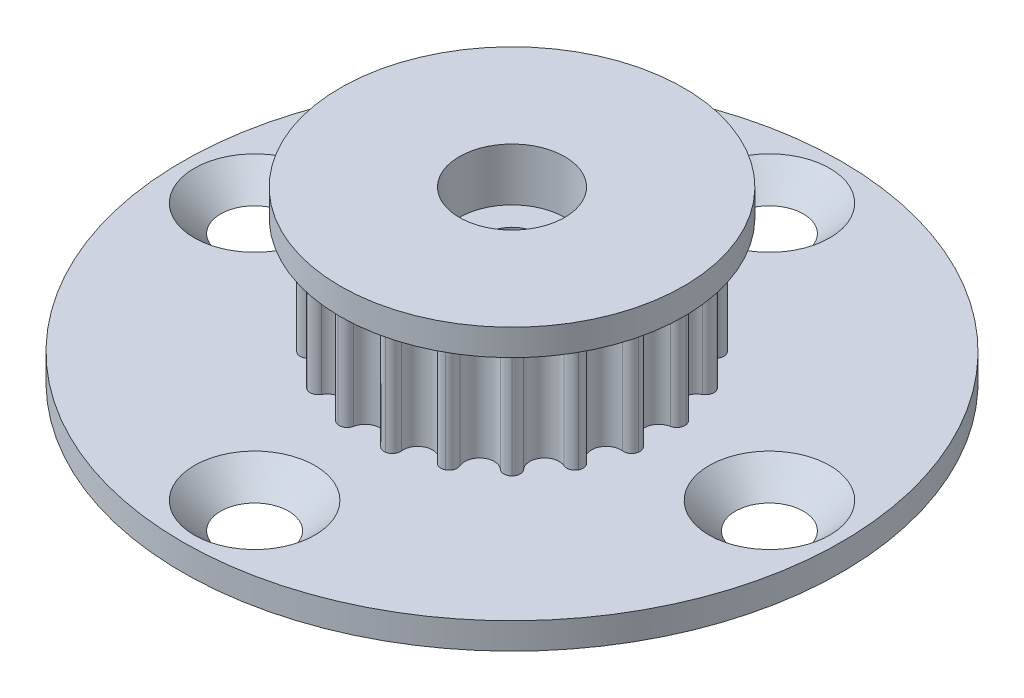
SolidWorks part; units mm, degrees
ref_plane "Front Plane" through (0, 0, 0) normal (0, 0, 1) x (1, 0, 0)
ref_plane "Top Plane" through (0, 0, 0) normal (0, 1, 0) x (1, 0, 0)
ref_plane "Right Plane" through (0, 0, 0) normal (1, 0, 0) x (0, 0, -1)
sketch "Sketch1" plane through (0, 0, 0) normal (0, 1, 0) x (1, 0, 0)
  line L0 (0, 0) -> (0, 9.1676) construction
  line L1 (0, 0) -> (2.731, 8.405) construction
  circle A0 centre (0, 0) radius 9.1676 construction
  circle A1 centre (0, 0) radius 7.9476 construction
  circle A2 centre (0, 8.8376) radius 0.89 construction
  circle A5 centre (2.731, 8.405) radius 0.89 construction
  arc A6 (0, 7.9476) -> (0.8721, 8.6598) centre (0, 8.8376) ccw
  arc A7 (0.8721, 8.6598) -> (1.4405, 9.0537) centre (1.362, 8.5599) cw
  arc A8 (1.4277, 9.0557) -> (1.8466, 8.5054) centre (1.3498, 8.5618) cw
  arc A9 (2.4559, 7.5586) -> (1.8466, 8.5054) centre (2.731, 8.405) cw
  arc A10 (1.4405, 9.0537) -> (1.4277, 9.0557) centre (0, 0) cw
  arc A11 (0, 7.9476) -> (2.4559, 7.5586) centre (0, 0) ccw
  dimension "D1" = 18.3352
  dimension "D3" = 1.78
  dimension "D4" = 0.5
  dimension "D2" = 1.22
  dimension "D5" = 18
extrude "Boss-Extrude1" add sketch "Sketch1" along normal mid plane 7.112 contours A6 A11 A9 A8 A7 region at (0.0089, 0, -0.0564)
ref_axis "Axis1" through (0, 3.3, 0) along (0, -1, 0)
pattern_circular "CirPattern1" count 20 over 360 about axis through (0, 3.3, 0) along (0, -1, 0) of "Boss-Extrude1"
sketch "Sketch2" plane through (0, 0, 0) normal (1, 0, 0) x (0, 0, -1)
  line L10 (0, 3.5) -> (10.3423, 3.5) construction
  line L11 (0, 3.5) -> (0, 5.0875) construction
  line L12 (0, 5.0875) -> (10.3423, 5.0875) construction
  line L15 (10.3423, 3.5) -> (10.3423, 5.0875) construction
  line L20 (0, 3.3) -> (0, -3.3) construction
  line L22 (10.3423, 5.0875) -> (0, 5.0875)
  line L23 (10.3423, 5.0875) -> (10.3423, 3.5)
  line L24 (10.3423, 3.5) -> (0, 3.5)
  line L25 (0, 5.0875) -> (0, 3.5)
  dimension "D1" = 1.5875
  dimension "D2" = 10.3423
  dimension "D3" = 3.5
revolve "Revolve3" add sketch "Sketch2" angle 360 about axis through (0, 3.3, 0) along (0, -1, 0) region at (0, 4.2937, -5.1712)
mirror "Mirror1" about plane through (0, 0, 0) normal (0, 1, 0) of "Revolve3"
sketch "Sketch9" plane through (0, -5.0875, 0) normal (0, -1, 0) x (1, 0, 0)
  circle A0 centre (0, 0) radius 19.8438
  circle A1 centre (0, 0) radius 1.5
  dimension "D1" = 3
  dimension "D2" = 39.6875
extrude "Boss-Extrude2" add sketch "Sketch9" against normal up to surface (1.5875 mm away) up to face at (0, -3.5, 0)
sketch "Sketch3" plane through (0, 0, 0) normal (0, 1, 0) x (1, 0, 0)
  circle A0 centre (-15.5, 0) radius 1.7462
  circle A3 centre (0, 15.5) radius 1.7462
  circle A4 centre (15.5, 0) radius 1.7463
  circle A5 centre (0, -15.5) radius 1.7462
  dimension "D3" = 3.4925
  dimension "D1" = 15.5
  dimension "D4" = 4
extrude "Cut-Extrude1" cut sketch "Sketch3" against normal through all both and the other way through all
ref_axis "Axis2" through (-15.5, -5.0875, 0) along (0, 1, 0)
sketch "Sketch6" plane through (0, 0, 0) normal (0, 0, 1) x (1, 0, 0)
  line L0 (-19.1322, -3.5) -> (-11.8678, -3.5) construction
  line L1 (-13.7538, -3.5) -> (-17.2462, -3.5) construction
  line L2 (-11.8678, -3.5) -> (-15.5, -7.1322)
  line L3 (-15.5, -7.1322) -> (-19.1322, -3.5) construction
  line L4 (-18.548, -4.0842) -> (-12.452, -4.0842) construction
  line L5 (-17.2462, -3.998) -> (-13.7538, -3.998) construction
  line L8 (-15.5, -7.1322) -> (-15.5, -3.5)
  line L9 (-15.5, -3.5) -> (-11.8678, -3.5)
  line L10 (-15.5, -5.0875) -> (-15.5, -3.5) construction
  line L12 (-17.2462, -3.5) -> (-17.2462, -5.0875) construction
  line L13 (-13.7538, -5.0875) -> (-13.7538, -3.5) construction
  point P2 (-15.5, -3.998)
  dimension "D1" = 6.096
  dimension "D2" = 0.5842
revolve "Cut-Revolve2" cut sketch "Sketch6" angle 360 about axis through (-15.5, -5.0875, 0) along (0, 1, 0)
pattern_circular "CirPattern2" count 4 over 360 about axis through (0, 3.3, 0) along (0, -1, 0) of "Cut-Revolve2"
sketch "Sketch12" plane through (0, 5.0875, 0) normal (0, 1, 0) x (1, 0, 0)
  circle A0 centre (0, 0) radius 3.175
  dimension "D1" = 6.35
extrude "Cut-Extrude2" cut sketch "Sketch12" against normal blind 3.175 from surface starting at face at (0, 5.0875, 10.3423)
sketch "Sketch13" plane through (0, 1.9125, 0) normal (0, 1, 0) x (1, 0, 0)
  circle A0 centre (0, 0) radius 1.525
  dimension "D1" = 3.05
extrude "Cut-Extrude4" cut sketch "Sketch13" against normal through all contours A0
equation "\"TEETH_NUM\"= 20"
equation "\"TOOTH_PITCH\"= 3mm"
equation "\"PITCH_LINE_OFFSET\"= .015in"
equation "\"DIAMETER_PER_GROOVE\"= \"OUTSIDE_DIAMETER\" / \"TEETH_NUM\" * 1in"
equation "\"PITCH_DIAMETER\"= ( ( \"TEETH_NUM\" * 3 - 1.31 ) / 3.1415 + .415 ) * 1mm"
equation "\"OUTSIDE_DIAMETER\"= \"PITCH_DIAMETER\" - \"PITCH_LINE_OFFSET\" * 2"
equation "\"D1@Sketch1\"=\"OUTSIDE_DIAMETER\""
equation "\"TOOTH_HEIGHT\"= 1.22mm"
equation "\"D2@Sketch1\"=\"TOOTH_HEIGHT\""
equation "\"TOOTH_DIAMETER\"= 1.78mm"
equation "\"INTERNAL_RADIUS\"= .5mm"
equation "\"D3@Sketch1\"=\"TOOTH_DIAMETER\""
equation "\"D5@Sketch1\"=360 / \"TEETH_NUM\""
equation "\"D4@Sketch1\"=\"INTERNAL_RADIUS\""
equation "\"D1@CirPattern1\"=\"TEETH_NUM\""
equation "\"BELT_GAP\"= 7mm"
equation "\"D2@Sketch2\"=\"PITCH_DIAMETER\"/2+1/32"
equation "\"D3@Sketch2\"=\"BELT_GAP\"/2"
